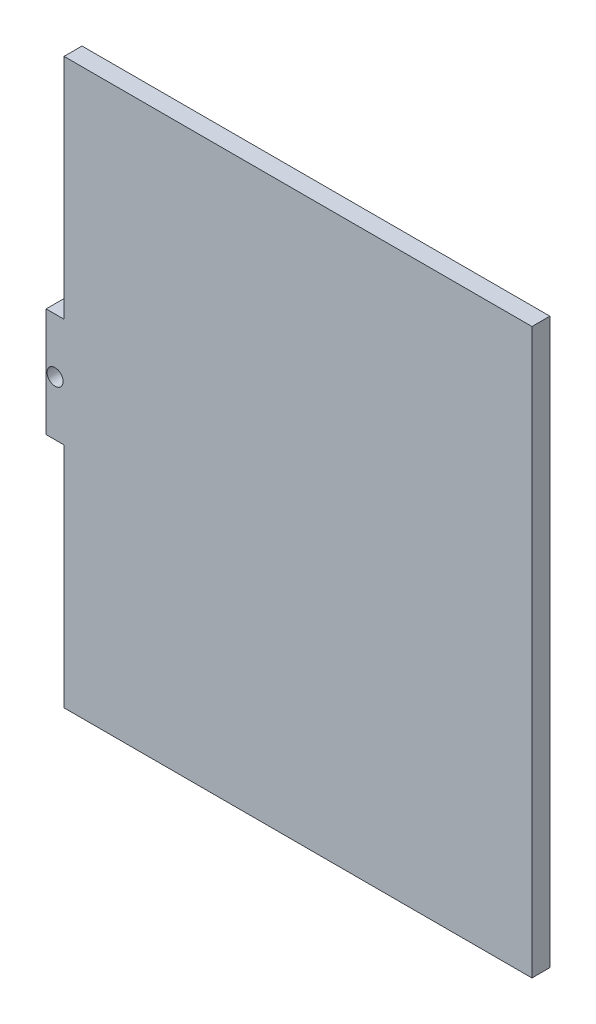
SolidWorks part; units mm, degrees
ref_plane "Front Plane" through (0, 0, 0) normal (0, 0, 1) x (1, 0, 0)
ref_plane "Top Plane" through (0, 0, 0) normal (0, 1, 0) x (1, 0, 0)
ref_plane "Right Plane" through (0, 0, 0) normal (1, 0, 0) x (0, 0, -1)
sketch "Sketch1" plane through (0, 0, 0) normal (0, 0, 1) x (1, 0, 0)
  line L0 (-41.465, 50) -> (-13.8217, 50)
  line L1 (-41.465, -50) -> (41.465, -50)
  line L2 (-41.465, -50) -> (-41.465, 50)
  line L3 (-41.465, 50) -> (41.465, 50) construction
  line L4 (41.465, -50) -> (41.465, 50)
  line L5 (-41.465, -50) -> (41.465, 50) construction
  line L6 (-41.465, 50) -> (41.465, -50) construction
  line L7 (-13.8217, 50) -> (13.8217, 50)
  line L8 (13.8217, 50) -> (41.465, 50)
  point P0 (0, 0)
  dimension "D1" = 82.93
  dimension "D2" = 100
extrude "Boss-Extrude1" add sketch "Sketch1" along normal blind 3.18
sketch "Sketch3" [suppressed] plane through (0, 0, 0) normal (0, 0, -1) x (-1, 0, 0)
  line L0 (-33.5967, 34.1533) -> (-33.5967, -62.5967)
  line L1 (-33.5967, -62.5967) -> (32.7533, -62.5967)
  line L2 (32.7533, -62.5967) -> (32.7533, 34.1533)
  line L3 (32.7533, 34.1533) -> (9.0783, 34.1533)
  line L4 (9.0783, 34.1533) -> (9.0783, 37.1533)
  line L5 (9.0783, 37.1533) -> (-9.9217, 37.1533)
  line L6 (-9.9217, 37.1533) -> (-9.9217, 34.1533)
  line L7 (-9.9217, 34.1533) -> (-33.5967, 34.1533)
  line L8 (32.7533, 43.1533) -> (-33.5967, 43.1533)
  line L9 (32.7533, -62.5967) -> (32.7533, 43.1533)
  line L10 (-33.5967, -62.5967) -> (32.7533, -62.5967)
  line L11 (-33.5967, 43.1533) -> (-33.5967, -62.5967)
  line L12 (-33.5967, -62.5967) -> (-33.5967, -70.465) construction
  line L13 (41.465, -70.465) -> (-41.465, -70.465) construction
  line L14 (-33.5967, -62.5967) -> (-41.465, -62.5967) construction
  line L15 (-41.465, -70.465) -> (-41.465, 70.465) construction
  dimension "D1" = 66.35
  dimension "D2" = 96.75
  dimension "D3" = 105.75
  dimension "D4" = 19
  dimension "D5" = 3
extrude "Cut-Extrude1" [suppressed] cut sketch "Sketch3" against normal through all contours L6 L7 L0 L1 L2 L3 L4 L5
sketch "Sketch4" [suppressed] plane through (-50, 0, 0) normal (-1, 0, 0) x (0, 0, 1)
  line L0 (1.59, -73.645) -> (1.59, -24.6061) construction
  line L1 (3.18, -73.645) -> (0, -73.645) construction
  line L2 (1.59, 73.645) -> (1.59, 25.5724) construction
  line L3 (3.18, 73.645) -> (0, 73.645) construction
  line L4 (3.18, 73.645) -> (3.18, -73.645) construction
  line L5 (0, 35.2224) -> (3.18, 35.2224)
  line L6 (0, 35.2224) -> (0, 15.9224)
  line L7 (0, 15.9224) -> (3.18, 15.9224)
  line L8 (3.18, 35.2224) -> (3.18, 15.9224)
  line L9 (0, 35.2224) -> (3.18, 15.9224) construction
  line L10 (0, 15.9224) -> (3.18, 35.2224) construction
  line L12 (0, -34.2561) -> (3.18, -34.2561)
  line L13 (0, -34.2561) -> (0, -14.9561)
  line L14 (0, -14.9561) -> (3.18, -14.9561)
  line L15 (3.18, -34.2561) -> (3.18, -14.9561)
  line L16 (0, -34.2561) -> (3.18, -14.9561) construction
  line L17 (0, -14.9561) -> (3.18, -34.2561) construction
  dimension "D1" = 19.3
extrude "Boss-Extrude2" [suppressed] add sketch "Sketch4" along normal blind 3.18
sketch "Sketch5" [suppressed] plane through (0, 0, 3.18) normal (0, 0, 1) x (1, 0, 0)
  line L0 (-51.59, 35.2224) -> (-51.59, 15.9224) construction
  line L1 (-53.18, 35.2224) -> (-50, 35.2224) construction
  line L2 (-53.18, 15.9224) -> (-50, 15.9224) construction
  line L3 (-51.59, -14.9561) -> (-51.59, -34.2561) construction
  line L4 (-53.18, -14.9561) -> (-50, -14.9561) construction
  line L5 (-53.18, -34.2561) -> (-50, -34.2561) construction
  circle A0 centre (-51.59, 25.5724) radius 1.425
  circle A1 centre (-51.59, -24.6061) radius 1.425
extrude "Cut-Extrude2" [suppressed] cut sketch "Sketch5" against normal through all
sketch "Sketch6" [suppressed] plane through (41.465, 0, 0) normal (1, 0, 0) x (0, 0, -1)
  line L0 (-1.59, 70.465) -> (-1.59, 24.5447) construction
  line L1 (-3.18, 70.465) -> (0, 70.465) construction
  line L2 (-1.59, -70.465) -> (-1.59, -24.6386) construction
  line L3 (-3.18, -70.465) -> (0, -70.465) construction
  line L4 (0, -70.465) -> (0, 70.465) construction
  line L5 (-3.18, -34.2886) -> (0, -34.2886)
  line L6 (-3.18, -34.2886) -> (-3.18, -14.9886)
  line L7 (-3.18, -14.9886) -> (0, -14.9886)
  line L8 (0, -34.2886) -> (0, -14.9886)
  line L9 (-3.18, -34.2886) -> (0, -14.9886) construction
  line L10 (-3.18, -14.9886) -> (0, -34.2886) construction
  line L12 (-3.18, 34.1947) -> (0, 34.1947)
  line L13 (-3.18, 34.1947) -> (-3.18, 14.8947)
  line L14 (-3.18, 14.8947) -> (0, 14.8947)
  line L15 (0, 34.1947) -> (0, 14.8947)
  line L16 (-3.18, 34.1947) -> (0, 14.8947) construction
  line L17 (-3.18, 14.8947) -> (0, 34.1947) construction
  dimension "D1" = 19.3
extrude "Boss-Extrude3" [suppressed] add sketch "Sketch6" along normal blind 3.18
sketch "Sketch7" [suppressed] plane through (0, 0, 3.18) normal (0, 0, 1) x (1, 0, 0)
  line L0 (43.055, 34.1947) -> (43.055, 14.8947) construction
  line L1 (44.645, 34.1947) -> (41.465, 34.1947) construction
  line L2 (44.645, 14.8947) -> (41.465, 14.8947) construction
  line L3 (43.055, -14.9886) -> (43.055, -34.2886) construction
  line L4 (44.645, -14.9886) -> (41.465, -14.9886) construction
  line L5 (44.645, -34.2886) -> (41.465, -34.2886) construction
  circle A0 centre (43.055, 24.5447) radius 1.425
  circle A1 centre (43.055, -24.6386) radius 1.425
extrude "Cut-Extrude3" [suppressed] cut sketch "Sketch7" against normal through all
sketch "Sketch9" plane through (-41.465, 0, 0) normal (-1, 0, 0) x (0, 0, 1)
  line L0 (0, 0) -> (3.18, 0) construction
  line L1 (0, 50) -> (0, -50) construction
  line L2 (3.18, 50) -> (3.18, -50) construction
  line L4 (0, -9.65) -> (3.18, -9.65)
  line L5 (0, -9.65) -> (0, 9.65)
  line L6 (0, 9.65) -> (3.18, 9.65)
  line L7 (3.18, -9.65) -> (3.18, 9.65)
  line L8 (0, -9.65) -> (3.18, 9.65) construction
  line L9 (0, 9.65) -> (3.18, -9.65) construction
  point P6 (1.59, 0)
  dimension "D1" = 19.3
extrude "Boss-Extrude4" add sketch "Sketch9" along normal blind 3.18
sketch "Sketch10" plane through (0, 0, 3.18) normal (0, 0, 1) x (1, 0, 0)
  line L0 (-43.055, 9.65) -> (-43.055, -9.65) construction
  line L1 (-44.645, 9.65) -> (-41.465, 9.65) construction
  line L2 (-44.645, -9.65) -> (-41.465, -9.65) construction
  circle A0 centre (-43.055, 0) radius 1.425
extrude "Cut-Extrude4" cut sketch "Sketch10" against normal through all
